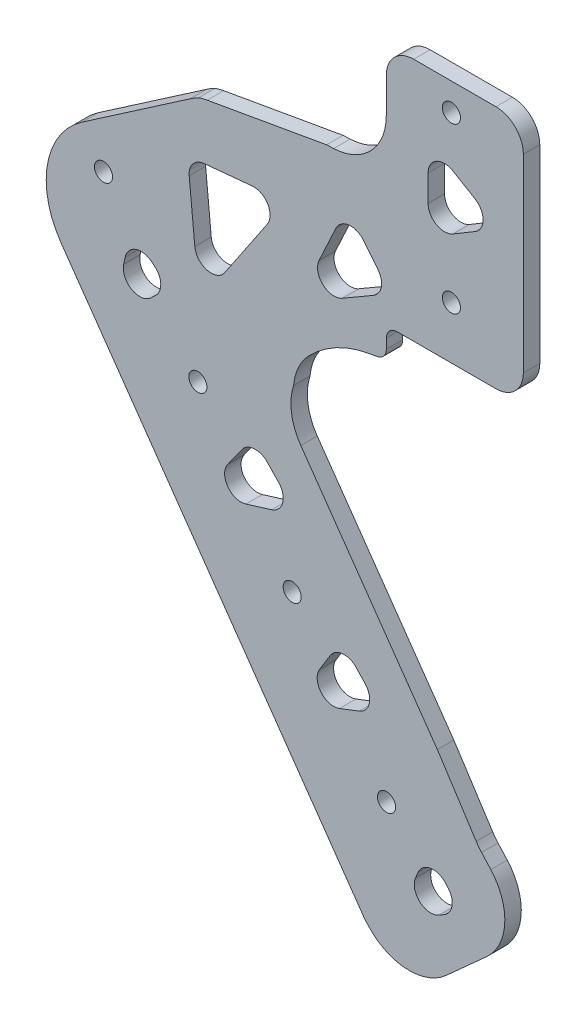
SolidWorks part; units mm, degrees
material "环氧树脂,未充填"
ref_plane "前视基准面" through (0, 0, 0) normal (0, 0, 1) x (1, 0, 0)
ref_plane "上视基准面" through (0, 0, 0) normal (0, 1, 0) x (1, 0, 0)
ref_plane "右视基准面" through (0, 0, 0) normal (1, 0, 0) x (0, 0, -1)
other "Configuration Table"
sketch "草图1" plane through (0, 0, 0) normal (0, 0, 1) x (1, 0, 0)
  line L0 (0, -30) -> (-76.6366, -43.5131)
  line L1 (0, 0) -> (29, 0)
  line L2 (0, 0) -> (0, -30)
  line L4 (29, 0) -> (29, -50)
  line L5 (29, -50) -> (29, -55.3493)
  line L6 (29, -55.3493) -> (-0.5442, -60.5588)
  line L7 (-11.9342, -93.6375) -> (28.3683, -138.398)
  line L8 (-94.2956, -47.0002) -> (6.074, -158.4719)
  line L10 (28.3683, -138.398) -> (6.074, -158.4719)
  line L11 (-76.6366, -43.5131) -> (-94.2956, -47.0002)
  circle A0 centre (14.5, -15) radius 1.65
  circle A1 centre (14.5, -45) radius 1.65
  arc A2 (-0.5442, -60.5588) -> (-11.9342, -93.6375) centre (2.9287, -80.2549) ccw
  point P17 (-36.077, -66.8242)
  dimension "D3" = 3.3
  dimension "D4" = 3.3
  dimension "D5" = 30
  dimension "D6" = 14.5
  dimension "D7" = 20
  dimension "D8" = 14.5
  dimension "D17" = 15
  dimension "D10" = 18
  dimension "D1" = 29
  dimension "D2" = 50
  dimension "D9" = 30
  dimension "D11" = 100
  dimension "30" = 30
  dimension "58" = 58
  dimension "D13" = 30
  dimension "D15" = 150
  dimension "D16" = 30
extrude "凸台-拉伸1" add sketch "草图1" along normal blind 3
sketch "草图2" plane through (0, 0, 3) normal (0, 0, 1) x (1, 0, 0)
  line L0 (-37.5097, -36.614) -> (-44.1108, -102.736)
  line L1 (0, -30) -> (-76.6366, -43.5131) construction
  line L2 (-94.2956, -47.0002) -> (6.074, -158.4719) construction
  line L3 (-37.5097, -36.614) -> (-120.9749, -15.6483)
  line L4 (-120.9749, -15.6483) -> (-92.2325, -102.736)
  line L5 (-92.2325, -102.736) -> (-44.1108, -102.736)
extrude "切除-拉伸1" cut sketch "草图2" against normal blind 3
fillet "圆角1" radius 10 8 edges at (6.074, -158.4719, 1.5) (28.3683, -138.398, 1.5) (29, -55.3493, 1.5) (29, 0, 1.5) (0, 0, 1.5) (0, -30, 1.5) (-44.1108, -102.736, 1.5) (-37.5097, -36.614, 1.5)
sketch "草图3" plane through (0, 0, 3) normal (0, 0, 1) x (1, 0, 0)
  line L0 (-15.9816, -73.7436) -> (19.462, -128.5065)
  line L1 (21.677, -130.9665) -> (-11.9342, -93.6375) construction
  line L2 (-15.9816, -73.7436) -> (-25.5123, -91.2997)
  line L3 (-25.5123, -91.2997) -> (19.462, -128.5065)
  arc A0 (-0.5442, -60.5588) -> (-11.9342, -93.6375) centre (2.9287, -80.2549) ccw construction
  point P7 (19.462, -128.5065)
extrude "凸台-拉伸2" add sketch "草图3" against normal blind 3
fillet "圆角2" radius 10 2 edges at (19.462, -128.5065, 1.5) (-15.9816, -73.7436, 1.5)
sketch "草图6" plane through (0, 0, 0) normal (0, 0, 1) x (1, 0, 0)
  line L2 (2451.2221, -2.4123) -> (2347.9783, -149.8596)
  line L3 (2475.7966, -19.6196) -> (2372.5529, -167.0669)
  line L12 (2451.2221, -2.4123) -> (2475.7966, -19.6196)
  line L13 (2347.9783, -149.8596) -> (2372.5529, -167.0669)
  line L14 (1191.5041, 76.2763) -> (1191.5041, -295.0217) construction
  line L15 (35.0299, -149.8596) -> (10.4553, -167.0669)
  line L16 (-68.2139, -2.4123) -> (-92.7884, -19.6196)
  line L17 (-92.7884, -19.6196) -> (10.4553, -167.0669)
  line L18 (-68.2139, -2.4123) -> (35.0299, -149.8596)
  line L19 (-55.5222, -72.8412) -> (-87.6721, -95.3528)
  line L20 (-87.6721, -95.3528) -> (10.4553, -167.0669)
  line L21 (35.0299, -149.8596) -> (-20.129, -71.0847)
  line L22 (-14.2733, -72.4337) -> (35.0299, -149.8596)
  line L23 (-14.2733, -72.4337) -> (-17.5687, -74.7411)
  circle A1 centre (14.5, -15) radius 1.65
  circle A2 centre (2431.9627, -56.0693) radius 1.65
  circle A3 centre (14.5, -45) radius 1.65
  circle A4 centre (2380.3408, -129.793) radius 1.65
  circle A5 centre (-31.7472, -80.6438) radius 1.65
  circle A6 centre (2397.5481, -105.2184) radius 1.65
  circle A7 centre (2414.7554, -80.6438) radius 1.65
  circle A9 centre (-14.5399, -105.2184) radius 1.65
  circle A10 centre (2368.5082, -45) radius 1.65
  circle A11 centre (2.6674, -129.793) radius 1.65
  circle A12 centre (2368.5082, -15) radius 1.65
  circle A20 centre (-48.9545, -56.0693) radius 1.65
  circle A21 centre (14.5, -15) radius 1.65 construction
  arc A22 (-11.5618, -66.47) -> (-12.7116, -78.7959) centre (-4.3166, -73.3625) ccw construction
  point P41 (0, 0)
  dimension "D1" = 3.3
  dimension "D2" = 3.3
  dimension "D3" = 3.3
  dimension "D4" = 3.3
  dimension "D6" = 15
  dimension "D7" = 15
  dimension "D9" = 15
  dimension "D11" = 30
  dimension "D12" = 3.3
  dimension "D13" = 3.3
  dimension "D14" = 60.2184
  dimension "D15" = 55
  dimension "D17" = 46.2472
  dimension "D5" = 30
  dimension "D8" = 15
  dimension "D10" = 60.5352
  dimension "D16" = 180
extrude "切除-拉伸2" cut sketch "草图6" along normal blind 33 contours L19 L20 L17 | L22 L23 L21 | A5 | A9 | A11 region at (1.0626, -99.0115, 0) region at (-44.2463, -111.7536, 0) region at (-31.7472, -80.6438, 0) region at (-14.5399, -105.2184, 0)
fillet "圆角3" radius 10 1 edges at (-17.5687, -74.7411, 1.5)
fillet "圆角4" radius 10 1 edges at (-42.9227, -90.8352, 1.5)
sketch "草图7" plane through (0, 0, 3) normal (0, 0, 1) x (1, 0, 0)
  line L1 (-34.5661, -102.7696) -> (-65.3734, -58.7723)
  line L2 (-1.2885, -150.2951) -> (-40.7952, -93.8735) construction
  line L4 (-31.5857, -35.5578) -> (-34.5661, -102.7696)
  line L5 (-65.3734, -58.7723) -> (-42.0908, -16.5195)
  line L6 (-42.0908, -16.5195) -> (-31.5857, -35.5578)
extrude "凸台-拉伸3" add sketch "草图7" against normal blind 3
sketch "草图8" plane through (0, 0, 3) normal (0, 0, 1) x (1, 0, 0)
  line L0 (2.6674, -129.793) -> (-14.5399, -105.2184) construction
  line L1 (-14.5399, -105.2184) -> (-82.827, -7.6943) construction
  circle A0 centre (-48.9545, -56.0693) radius 1.65
  circle A1 centre (-31.7472, -80.6438) radius 1.65 construction
  dimension "D1" = 3.3
  dimension "D2" = 30
extrude "切除-拉伸3" cut sketch "草图8" against normal blind 4
sketch "草图9" plane through (0, 0, 3) normal (0, 0, 1) x (1, 0, 0)
  line L0 (-31.5857, -35.5578) -> (-42.0908, -16.5195)
  line L1 (-42.0908, -16.5195) -> (-65.3734, -58.7723)
  line L2 (-65.3734, -58.7723) -> (-31.5857, -35.5578)
extrude "切除-拉伸5" cut sketch "草图9" against normal blind 4
fillet "圆角6" radius 15 1 edges at (-65.3734, -58.7723, 1.5)
fillet "圆角7" radius 15 1 edges at (-31.5857, -35.5578, 1.5)
sketch "草图10" plane through (0, 0, 3) normal (0, 0, 1) x (1, 0, 0)
  line L0 (-33.6168, -45.8813) -> (-31.4972, -67.8818)
  line L1 (-31.4972, -67.8818) -> (-15.5479, -44.1405)
  line L2 (-15.5479, -44.1405) -> (-33.6168, -45.8813)
  line L3 (-4.5422, -39.4038) -> (-13.6359, -59.0462)
  line L4 (-13.6359, -59.0462) -> (3.2784, -49.225)
  line L5 (3.2784, -49.225) -> (-4.5422, -39.4038)
  line L6 (-21.5957, -84.3826) -> (-31.4972, -98.1969)
  line L7 (-31.4972, -98.1969) -> (-13.6359, -92.6712)
  line L8 (-13.6359, -92.6712) -> (-21.5957, -84.3826)
  line L9 (-43.9616, -62.8061) -> (-47.3823, -78.4623)
  line L10 (-47.3823, -78.4623) -> (-36.9826, -68.4751)
  line L11 (-36.9826, -68.4751) -> (-43.9616, -62.8061)
  line L12 (-5.5448, -108.4589) -> (-14.1948, -122.4947)
  line L13 (-14.1948, -122.4947) -> (1.8228, -116.3527)
  line L14 (1.8228, -116.3527) -> (-5.5448, -108.4589)
  line L15 (10.2429, -133.5877) -> (4.5478, -147.4164)
  line L16 (4.5478, -147.4164) -> (16.2948, -140.502)
  line L17 (16.2948, -140.502) -> (10.2429, -133.5877)
  line L18 (10.2429, -21.377) -> (10.2429, -36.7166)
  line L19 (10.2429, -36.7166) -> (23.1459, -29.0468)
  line L20 (23.1459, -29.0468) -> (10.2429, -21.377)
extrude "切除-拉伸6" cut sketch "草图10" against normal blind 4 contours L1 L2 L0 | L4 L5 L3 | L19 L20 L18 | L10 L11 L9 | L7 L8 L6 | L13 L14 L12 | L16 L17 L15 region at (-26.8873, -52.6345, 3) region at (-4.9666, -49.225, 3) region at (-22.2429, -91.7502, 3) region at (-42.7755, -69.9145, 3) region at (-5.9723, -115.7688, 3) region at (10.3618, -140.502, 3) region at (14.5439, -29.0468, 3)
fillet "圆角8" radius 3 21 edges at (-33.6168, -45.8813, 1.5) (-15.5479, -44.1405, 1.5) (-31.4972, -67.8818, 1.5) (-4.5422, -39.4038, 1.5) (3.2784, -49.225, 1.5) (-13.6359, -59.0462, 1.5) (23.1459, -29.0468, 1.5) (10.2429, -36.7166, 1.5) (-43.9616, -62.8061, 1.5) (-36.9826, -68.4751, 1.5) (-47.3823, -78.4623, 1.5) (-21.5957, -84.3826, 1.5) (-13.6359, -92.6712, 1.5) (-31.4972, -98.1969, 1.5) (-5.5448, -108.4589, 1.5) (1.8228, -116.3527, 1.5) (-14.1948, -122.4947, 1.5) (10.2429, -133.5877, 1.5) (16.2948, -140.502, 1.5) (4.5478, -147.4164, 1.5) (10.2429, -21.377, 1.5)
sketch "草图13" plane through (0, 0, 3) normal (0, 0, 1) x (1, 0, 0)
  line L0 (19, 0) -> (10, 0) construction
  line L1 (7.6193, -10) -> (22.6193, -10)
  line L2 (2.6193, -15) -> (2.6193, -54.5529)
  line L3 (2.6193, -54.5529) -> (22.6193, -54.5529)
  line L4 (27.6193, -15) -> (27.6193, -49.5529)
  line L5 (73.1141, -54.5529) -> (74.0243, -54.5529)
  line L6 (2.6193, -15) -> (-5.703, -15)
  line L8 (2.6193, 7.0726) -> (-5.703, 7.0726)
  line L9 (-5.703, -15) -> (-5.703, 7.0726)
  line L10 (54.3641, -15) -> (73.1141, -15)
  line L11 (27.6193, -15) -> (27.6193, -49.5529)
  line L13 (73.1141, -15) -> (73.1141, -59.7579)
  line L14 (2.6193, -15) -> (27.6193, -15)
  line L15 (2.6193, 7.0726) -> (2.6193, 12.2289)
  line L16 (2.6193, 12.2289) -> (54.3641, 12.2289)
  line L17 (54.3641, -15) -> (54.3641, 12.2289)
  line L18 (2.6193, -54.5529) -> (22.6193, -54.5529)
  line L19 (2.6193, -54.5529) -> (2.6193, -81.6759)
  line L20 (2.6193, -81.6759) -> (74.0243, -81.6759)
  line L21 (74.0243, -54.5529) -> (74.0243, -81.6759)
  line L23 (2.6193, -15) -> (-8.2635, -15)
  line L24 (2.6193, -15) -> (2.6193, -31.4571)
  line L25 (2.6193, -31.4571) -> (-8.2635, -31.4571)
  line L26 (-8.2635, -15) -> (-8.2635, -31.4571)
  arc A1 (22.6193, -54.5529) -> (27.6193, -49.5529) centre (22.6193, -49.5529) ccw
  arc A2 (7.6193, -10) -> (2.6193, -15) centre (7.6193, -15) ccw
  arc A3 (22.6193, -10) -> (27.6193, -15) centre (22.6193, -15) cw
  point P10 (2.6193, -10)
  point P13 (27.6193, -10)
  dimension "D3" = 5
  dimension "D1" = 25
  dimension "D2" = 10
extrude "切除-拉伸7" cut sketch "草图13" against normal blind 4 contours L1 A3 L4 A1 L3 L19 L20 L21 L5 L13 L10 L17 L16 L15 L8 L9 L6 A2 region at (38.9136, -37.5525, 3)
fillet "圆角11" radius 2 2 edges at (2.6193, -54.5529, 1.5) (2.6193, -60.001, 1.5)
fillet "圆角12" radius 10 1 edges at (0, -15, 1.5)
sketch "草图14" plane through (0, 0, 3) normal (0, 0, 1) x (1, 0, 0)
  line L0 (2.6193, -15) -> (2.6193, -31.0187)
  line L1 (2.6193, -31.0187) -> (-8.2635, -31.4571)
  line L2 (-8.2635, -31.4571) -> (-8.2635, -7.081)
  line L3 (-8.2635, -7.081) -> (2.6193, -15)
extrude "切除-拉伸8" cut sketch "草图14" against normal blind 4
fillet "圆角13" radius 10 1 edges at (2.6193, -31.0187, 1.5)
